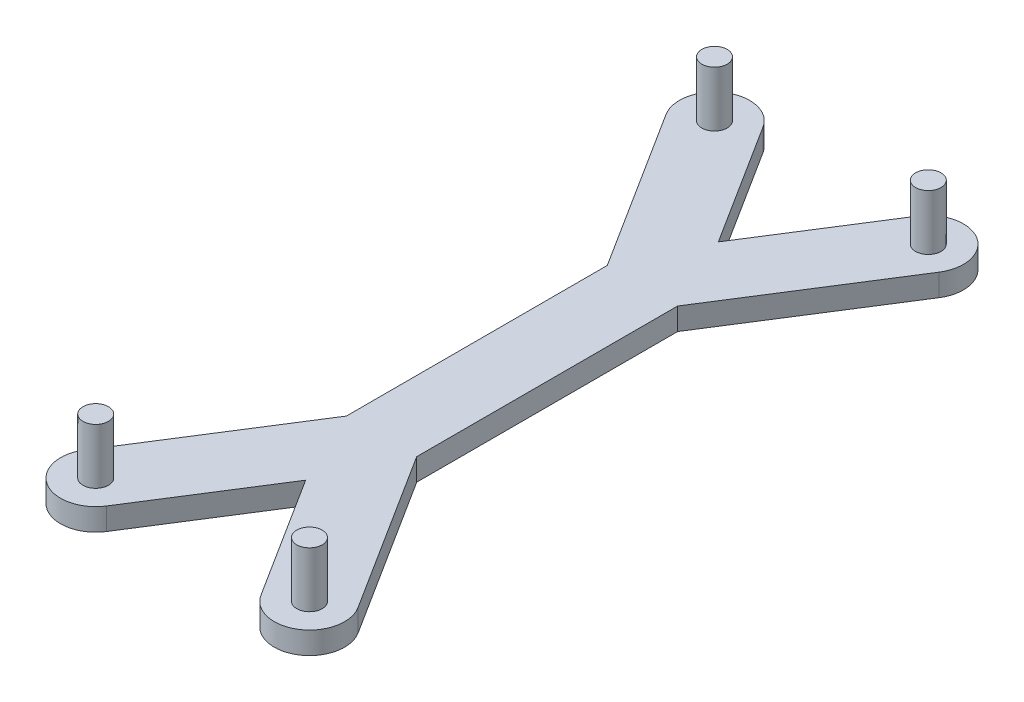
SolidWorks part; units mm, degrees
ref_plane "Front Plane" through (0, 0, 0) normal (0, 0, 1) x (1, 0, 0)
ref_plane "Top Plane" through (0, 0, 0) normal (0, 1, 0) x (1, 0, 0)
ref_plane "Right Plane" through (0, 0, 0) normal (1, 0, 0) x (0, 0, -1)
sketch "Sketch1" plane through (0, 0, 0) normal (0, 1, 0) x (1, 0, 0)
  line L0 (-14.0965, 0) -> (0, 0) construction
  line L1 (-12.3343, 26.2412) -> (-2.6823, 11.0012)
  line L2 (-9.652, 27.94) -> (0, 12.7) construction
  line L3 (0, 12.7) -> (0, -12.7) construction
  line L4 (-9.652, -27.94) -> (0, -12.7) construction
  line L5 (9.652, 27.94) -> (0, 12.7) construction
  line L6 (9.652, -27.94) -> (0, -12.7) construction
  line L7 (12.3343, -26.2412) -> (2.6823, -11.0012)
  line L8 (-6.9697, -29.6388) -> (2.6823, -14.3988)
  line L9 (-3.175, 12.7) -> (-3.175, -12.7)
  line L10 (6.9697, 29.6388) -> (-2.6823, 14.3988)
  line L11 (-6.9697, 29.6388) -> (2.6823, 14.3988)
  line L12 (6.9697, -29.6388) -> (-2.6823, -14.3988)
  line L13 (-12.3343, -26.2412) -> (-2.6823, -11.0012)
  line L14 (3.175, 12.7) -> (3.175, -12.7)
  line L15 (12.3343, 26.2412) -> (2.6823, 11.0012)
  circle A0 centre (-9.652, 27.94) radius 1.15
  circle A1 centre (9.652, 27.94) radius 1.15
  circle A2 centre (-9.652, -27.94) radius 1.15
  circle A3 centre (9.652, -27.94) radius 1.15
  arc A4 (-12.3343, 26.2412) -> (-6.9697, 29.6388) centre (-9.652, 27.94) cw
  arc A5 (-2.6823, 11.0012) -> (2.6823, 14.3988) centre (0, 12.7) ccw
  arc A6 (12.3343, -26.2412) -> (6.9697, -29.6388) centre (9.652, -27.94) cw
  arc A7 (2.6823, -11.0012) -> (-2.6823, -14.3988) centre (0, -12.7) ccw
  arc A8 (-6.9697, -29.6388) -> (-12.3343, -26.2412) centre (-9.652, -27.94) cw
  arc A9 (2.6823, -14.3988) -> (-2.6823, -11.0012) centre (0, -12.7) ccw
  arc A10 (-3.175, 12.7) -> (3.175, 12.7) centre (0, 12.7) cw
  arc A11 (-3.175, -12.7) -> (3.175, -12.7) centre (0, -12.7) ccw
  arc A12 (6.9697, 29.6388) -> (12.3343, 26.2412) centre (9.652, 27.94) cw
  arc A13 (-2.6823, 14.3988) -> (2.6823, 11.0012) centre (0, 12.7) ccw
  point P6 (0, -7.7499)
  point P14 (0, 0)
  point P15 (0, 8.7529)
  point P16 (0, 14.8866)
  point P17 (0, 5.905)
  point P18 (0, 13.1341)
  point P39 (12.4371, 26.2196)
  point P40 (0, 0)
  dimension "D1" = 2.3
  dimension "D2" = 27.94
  dimension "D3" = 9.652
  dimension "D6" = 25.4
  dimension "D4" = 3.175
  dimension "D5" = 3.175
extrude "Boss-Extrude1" add sketch "Sketch1" along normal blind 5 contours A0 | A1 | A3 | A2
extrude "Boss-Extrude2" add sketch "Sketch1<3>" against normal blind 2 contours L9 A10 L10 L11 A4 L1 A0 | A12 L10 L11 A5 L14 L15 A1 | A7 L7 L14 L15 A5 L1 L9 L13 | A7 A11 A9 | A11 L12 L8 | A9 L8 L12 A6 L7 L14 A3 | A8 L8 L12 A7 L9 L13 A2 | A10 A13 A5 | L10 A10 L11 | A13 L9 L1 | A5 L15 L14 | A7 L13 L9 | A9 L14 L7 region at (-6.364, 0, -22.5377) region at (-3.0751, 0, -11.8081) region at (0, 0, 0) region at (0, 0, -12.7) region at (-3.0751, 0, 11.8081) region at (-6.364, 0, 22.5377) region at (0, 0, -16.5921) region at (6.364, 0, -22.5377) region at (3.0751, 0, -11.8081) region at (0, 0, 12.7) region at (0, 0, 16.5921) region at (3.0751, 0, 11.8081) region at (6.364, 0, 22.5377)
sketch "Sketch1<3>" plane through (0, 0, 0) normal (0, 1, 0) x (1, 0, 0) same geometry as "Sketch1"
equation "\"D2@Sketch1\"=1.23-0.13"
equation "\"D3@Sketch1\"=0.51-.13"
